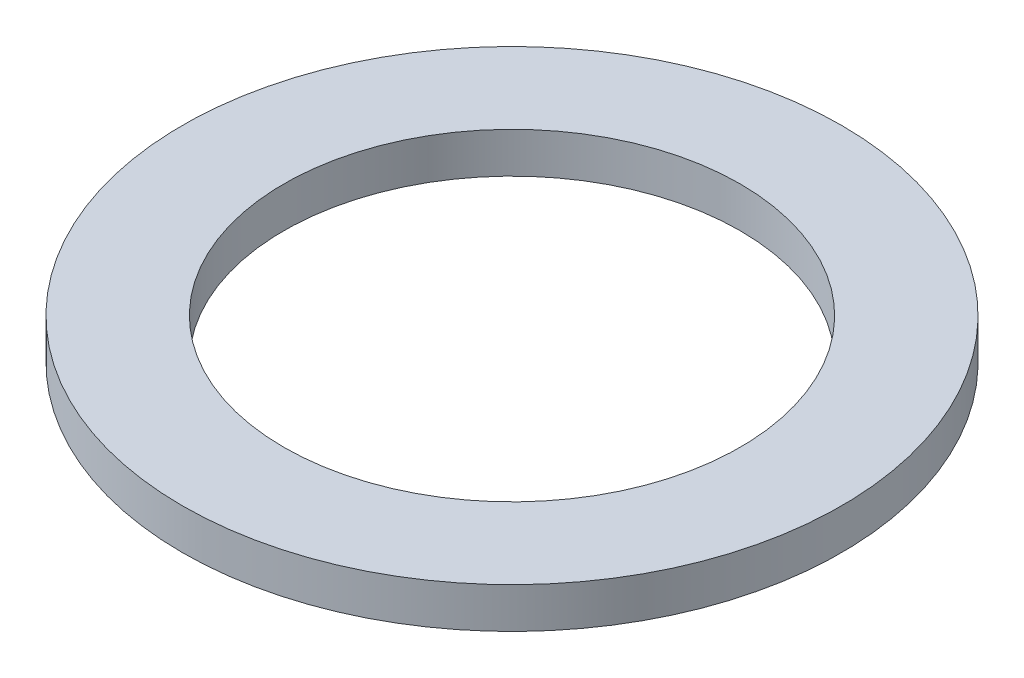
SolidWorks part; units mm, degrees
ref_plane "Front Plane" through (0, 0, 0) normal (0, 0, 1) x (1, 0, 0)
ref_plane "Top Plane" through (0, 0, 0) normal (0, 1, 0) x (1, 0, 0)
ref_plane "Right Plane" through (0, 0, 0) normal (1, 0, 0) x (0, 0, -1)
sketch "Sketch1" plane through (0, 0, 0) normal (0, 1, 0) x (1, 0, 0)
  circle A0 centre (0, 0) radius 32.5
  dimension "FLANGE_OD" = 65
extrude "Boss-Extrude1" add sketch "Sketch1" along normal blind 4
sketch "Sketch2" plane through (0, 0, 0) normal (0, 1, 0) x (1, 0, 0)
  circle A0 centre (0, 0) radius 22.5
  dimension "BORE_D" = 45
extrude "Cut-Extrude1" cut sketch "Sketch2" along normal through all
sketch "Sketch3" plane through (0, 4, 0) normal (0, 1, 0) x (1, 0, 0)
  circle A0 centre (0, 0) radius 14.7128 construction
  circle A1 centre (-14.7128, 0) radius 1.5318
  dimension "BOLT_D" = 3.0636
  dimension "BOLT_PCD" = 29.4257
extrude "Cut-Extrude2" cut sketch "Sketch3" against normal blind 3.5212 rebuild error yes
pattern_circular "CirPattern1" count 5 over 360 rebuild error yes
